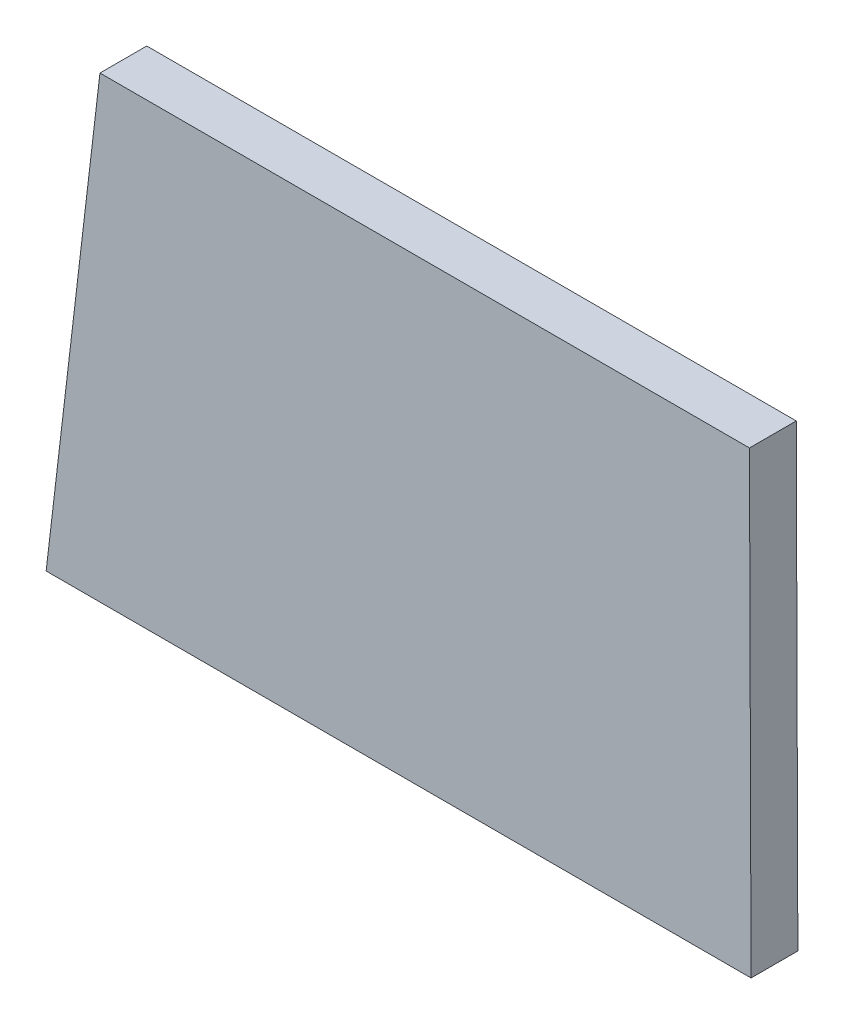
SolidWorks part; units mm, degrees
ref_plane "Ebene vorne" through (0, 0, 0) normal (0, 0, 1) x (1, 0, 0)
ref_plane "Ebene oben" through (0, 0, 0) normal (0, 1, 0) x (1, 0, 0)
ref_plane "Ebene rechts" through (0, 0, 0) normal (1, 0, 0) x (0, 0, -1)
sketch "Skizze1" plane through (0, 0, 0) normal (0, 0, 1) x (1, 0, 0)
  line L0 (0, 0) -> (2.3002, 19.5804)
  line L1 (2.3002, 19.5804) -> (30.0566, 19.5829)
  line L2 (30.0566, 19.5829) -> (30.125, 0)
  line L3 (30.125, 0) -> (0, 0)
  dimension "D1" = 30.125
  dimension "D2" = 19.583
  dimension "D3" = 19.715
  dimension "D4" = 83.3
  dimension "D5" = 89.8
extrude "Aufsatz-Linear austragen1" add sketch "Skizze1" along normal blind 2
sketch "Skizze4" plane through (0, 0, 0) normal (0, 0, 1) x (1, 0, 0)
  line L1 (0, 0) -> (30, 0)
  line L2 (0, 0) -> (0, 20)
  line L3 (0, 20) -> (30, 20)
  line L4 (30, 0) -> (30, 20)
  dimension "D1" = 30
  dimension "D2" = 20
sketch "Skizze2" plane through (0, 0, 2) normal (0, 0, 1) x (1, 0, 0)
  circle A0 centre (16.1795, 8.0246) radius 18.0602
sketch "Skizze3" plane through (0, 0, 2) normal (0, 0, 1) x (1, 0, 0)
  line L0 (2.1784, 0.7914) -> (30.1784, 0.7914)
  line L1 (2.1784, 0.7914) -> (2.1784, 18.7914)
  line L2 (30.1784, 0.7914) -> (30.1784, 18.7914)
  line L3 (2.1784, 18.7914) -> (30.1784, 18.7914)
  line L4 (2.1784, 0.7914) -> (30.1784, 18.7914) construction
  line L5 (30.1784, 0.7914) -> (2.1784, 18.7914) construction
  line L6 (30.125, 0) -> (30.0566, 19.5829) construction
  line L7 (30.0566, 19.5829) -> (2.3002, 19.5804) construction
  point P1 (16.1784, 9.7914)
  point P8 (30.0908, 9.7914)
  point P11 (16.1784, 19.5816)
  dimension "D1" = 18
  dimension "D2" = 28
ref_point "SWASI_Vision_Point_1"
ref_point "SWASI_Vision_Point_1_helper"
ref_point "SWASI_Vision_Point_2"
ref_point "SWASI_Vision_Point_2_helper"
ref_point "SWASI_Vision_Point_3"
ref_point "SWASI_Vision_Point_3_helper"
ref_point "SWASI_Vision_Point_4"
ref_plane "SWASI_Alignment_Plane_1" through (0, 0, 0) normal (0, -1, 0) x (-1, 0, 0)
ref_plane "SWASI_Alignment_Plane_2" through (0, 0, 2) normal (0, 0, -1) x (-1, 0, 0)
ref_axis "Achse3" through (0, 0, 2) along (0.9978, 0, -0.0662)
ref_axis "Achse4" through (0, 0, 0) along (0.9978, 0, 0.0662)
ref_point "SWASI_Surface_Center_Point"
ref_axis "SWASI_Norm_Alignment_Plane_3" through (30.125, 0, 0) along (-1, 0, 0)
ref_plane "SWASI_Alignment_Plane_3_G" through (15.0625, 0, 1) normal (-1, 0, 0) x (0, 0, 1)
